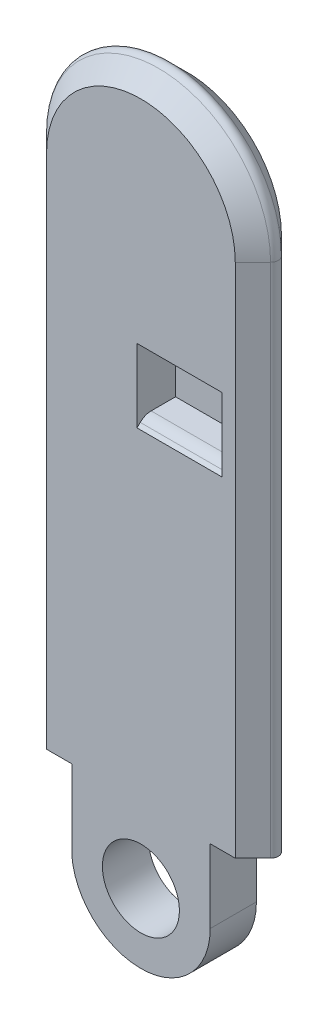
SolidWorks part; units mm, degrees
ref_plane "Płaszczyzna przednia" through (0, 0, 0) normal (0, 0, 1) x (1, 0, 0)
ref_plane "Płaszczyzna górna" through (0, 0, 0) normal (0, 1, 0) x (1, 0, 0)
ref_plane "Płaszczyzna prawa" through (0, 0, 0) normal (1, 0, 0) x (0, 0, -1)
sketch "Szkic1" plane through (0, 0, 0) normal (0, 0, 1) x (1, 0, 0)
  line L1 (-15.75, 33.5) -> (15.75, 33.5)
  line L2 (-15.75, 33.5) -> (-15.75, -33.5)
  line L3 (-15.75, -33.5) -> (15.75, -33.5)
  line L4 (15.75, 33.5) -> (15.75, -33.5)
  line L5 (-15.75, 33.5) -> (15.75, -33.5) construction
  line L6 (-15.75, -33.5) -> (15.75, 33.5) construction
  circle A0 centre (0, 33.5) radius 15.75
  point P0 (0, 0)
  dimension "D1" = 31.5
  dimension "D2" = 67
extrude "Dodanie-wyciągnięcie1" add sketch "Szkic1" against normal blind 6 contours L1 A0 | L1 A0 | A0 L2 L3 L4
chamfer "Sfazowanie1" distance 3.5 angle 45 6 edges at (15.75, 0, 0) (15.75, 0, -6) (0, 49.25, 0) (0, 49.25, -6) (-15.75, 0, 0) (-15.75, 0, -6)
fillet "Zaokrąglenie1" radius 1 3 edges at (15.25, 0, -3) (0, 48.75, -3) (-15.25, 0, -3)
sketch "Szkic2" plane through (0, 0, 0) normal (0, 0, 1) x (1, 0, 0)
  line L0 (-0.5, 12.25) -> (10.5, 12.25) construction
  line L1 (-10.6279, -13.75) -> (-5.9102, -13.75) construction
  line L10 (-0.5, 15) -> (-0.5, 9.5)
  line L11 (10.5, 9.5) -> (10.5, 15)
  line L12 (-0.5, 15) -> (10.5, 15)
  line L13 (-0.5, 9.5) -> (10.5, 9.5)
  line L14 (5, 15) -> (5, 9.5) construction
  point P15 (-8.269, -13.75)
  dimension "D1" = 5.5
  dimension "D2" = 11
  dimension "D3" = 5
  dimension "D4" = 13.75
  dimension "D5" = 26
extrude "Wytnij-wyciągnięcie1" cut sketch "Szkic2" against normal blind 5
sketch "Szkic3" plane through (0, 0, -6) normal (0, 0, -1) x (-1, 0, 0)
  line L2 (6, -24) -> (6, -27.9889) construction
  line L4 (1.5, -31.2389) -> (10.5, -31.2389)
  line L5 (1.5, -31.2389) -> (1.5, -24.7389)
  line L6 (1.5, -24.7389) -> (10.5, -24.7389)
  line L7 (10.5, -31.2389) -> (10.5, -24.7389)
  line L8 (1.5, -31.2389) -> (10.5, -24.7389) construction
  line L9 (1.5, -24.7389) -> (10.5, -31.2389) construction
  dimension "D2" = 9
  dimension "D3" = 6.5
extrude "Wytnij-wyciągnięcie2" cut sketch "Szkic3" against normal blind 4.5
chamfer "Sfazowanie2" distance 0.5 angle 45 1 edges at (-6, -24.7389, -6)
sketch "Szkic4" plane through (0, 0, 0) normal (0, 0, 1) x (1, 0, 0)
  line L0 (0, -33.5) -> (0, -43.0308) construction
  line L1 (-12.25, -33.5) -> (12.25, -33.5) construction
  line L2 (9, -43.0308) -> (9, -33.5)
  line L3 (9, -33.5) -> (-8.9747, -33.5)
  line L4 (-8.9747, -33.5) -> (-8.9747, -43.7054)
  circle A0 centre (0, -43.0308) radius 5
  circle A1 centre (0, -43.0308) radius 9
  dimension "D1" = 4
  dimension "D2" = 10
extrude "Dodanie-wyciągnięcie2" add sketch "Szkic4" against normal blind 6
sketch "Szkic5" plane through (0, 0, -6) normal (0, 0, -1) x (-1, 0, 0)
  line L3 (-5, 16) -> (0, 16)
  line L4 (0, 16) -> (0, -31)
  line L5 (-5, -31) -> (-5, 16)
  line L6 (-2.5, 16) -> (-2.5, -22.2858) construction
  line L8 (-0.5, 15) -> (-4.5, 15)
  line L9 (-0.5, 15) -> (-0.5, 9)
  line L10 (-0.5, 9) -> (-4.5, 9)
  line L11 (-4.5, 15) -> (-4.5, 9)
  line L12 (-0.5, 15) -> (-4.5, 9) construction
  line L13 (-0.5, 9) -> (-4.5, 15) construction
  point P6 (-2.5, 12)
  dimension "D1" = 1
  dimension "D2" = 0.5
  dimension "D3" = 6
  dimension "D4" = 5
  dimension "D5" = 16
  dimension "D6" = 2.5
extrude "Dodanie-wyciągnięcie3" add sketch "Szkic5" along normal blind 4.5 contours L8 L11 L10 L9
chamfer "Sfazowanie3" distance 3 angle 45 1 edges at (5, 15, 0)
chamfer "Sfazowanie4" distance 1 angle 45 1 edges at (5, 9.5, 0)
fillet "Zaokrąglenie2" radius 2 1 edges at (5, 9.5, -1)
